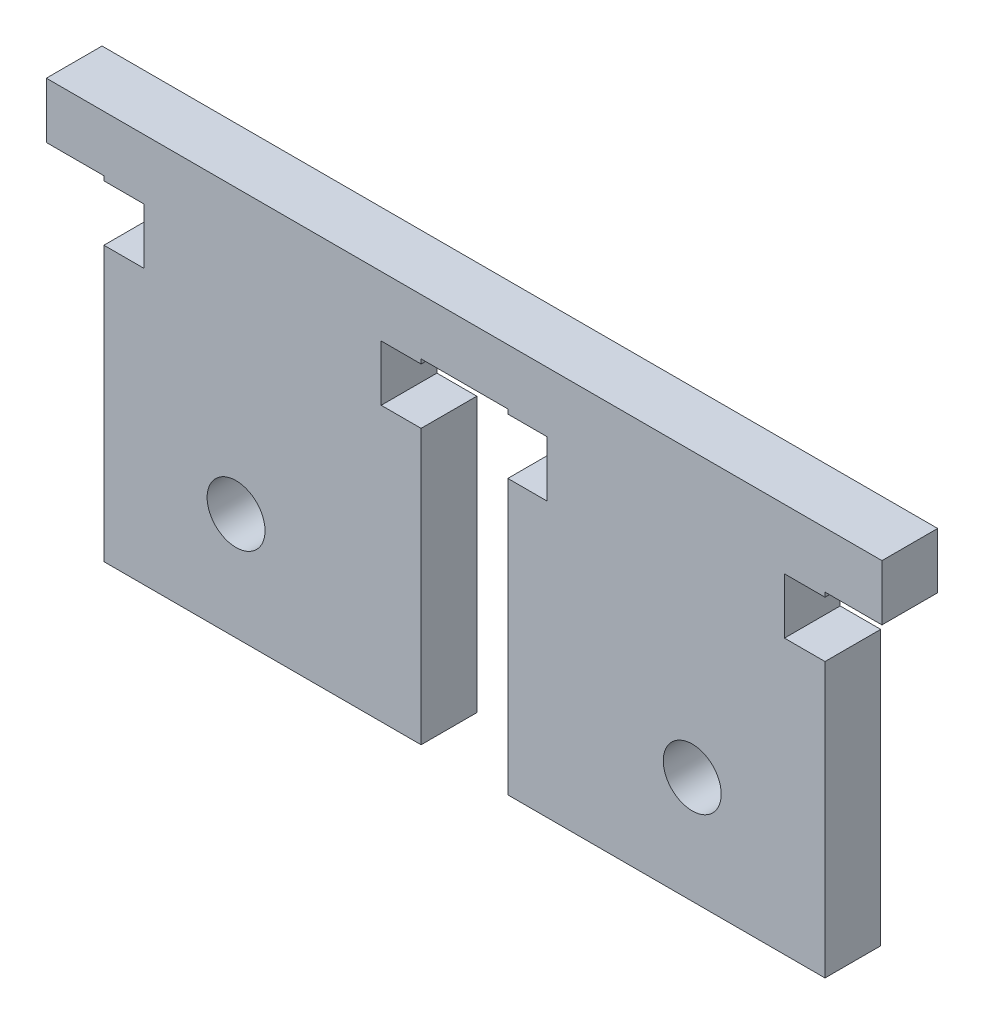
SolidWorks part; units mm, degrees
material "AISI 4130 Steel, annealed at 865C"
ref_plane "X-Y Datum" through (0, 0, 0) normal (0, 0, 1) x (1, 0, 0)
ref_plane "X-Z Datum" through (0, 0, 0) normal (0, 1, 0) x (1, 0, 0)
ref_plane "Y-Z Datum" through (0, 0, 0) normal (1, 0, 0) x (0, 0, -1)
sketch "Sketch3" plane through (0, 0, 0) normal (0, 0, 1) x (1, 0, 0)
  line L1 (-47.625, -30.48) -> (47.625, -30.48)
  line L2 (-47.625, -30.48) -> (-47.625, 30.48)
  line L3 (-47.625, 30.48) -> (47.625, 30.48)
  line L4 (47.625, -30.48) -> (47.625, 30.48)
  line L5 (-47.625, -30.48) -> (47.625, 30.48) construction
  line L6 (-47.625, 30.48) -> (47.625, -30.48) construction
  point P0 (0, 0)
  dimension "D1" = 95.25
  dimension "D2" = 60.96
extrude "Boss-Extrude1" add sketch "Sketch3" along normal blind 6.35
sketch "Sketch4" plane through (0, 0, 6.35) normal (0, 0, 1) x (1, 0, 0)
  line L0 (-47.625, 15.24) -> (-41.0616, 15.24)
  line L1 (-47.625, 30.48) -> (-47.625, -30.48) construction
  line L2 (-41.0616, 15.24) -> (-4.5491, 15.24)
  line L3 (-4.5491, 15.24) -> (4.6203, 15.24)
  line L4 (4.6203, 15.24) -> (41.1328, 15.24)
  line L5 (41.1328, 15.24) -> (47.625, 15.24)
  line L6 (47.625, -30.48) -> (47.625, 30.48) construction
  line L7 (0.0356, 15.24) -> (0.0356, -30.48) construction
  line L8 (-41.0616, 15.24) -> (-47.625, 15.24)
  line L9 (-41.0616, 15.24) -> (-41.0616, -30.48)
  line L10 (-41.0616, -30.48) -> (-47.625, -30.48)
  line L11 (-47.625, 15.24) -> (-47.625, -30.48)
  line L12 (-47.625, -30.48) -> (47.625, -30.48) construction
  line L13 (-1.5519, -16.0071) -> (1.6231, -16.0071)
  line L14 (-1.5519, -16.0071) -> (-1.5519, 0.7671)
  line L17 (-4.5491, 15.24) -> (4.6203, 15.24)
  line L19 (-4.9063, -30.48) -> (4.9774, -30.48)
  line L20 (-4.9063, -30.48) -> (-4.9063, 15.24)
  line L25 (-4.9063, 15.24) -> (4.9774, 15.24)
  line L26 (4.9774, -30.48) -> (4.9774, 15.24)
  line L27 (41.1328, 15.24) -> (47.625, 15.24)
  line L28 (41.1328, 15.24) -> (41.1328, -30.48)
  line L29 (41.1328, -30.48) -> (47.625, -30.48)
  line L31 (-4.9063, -30.48) -> (4.9774, 15.24) construction
  line L32 (-4.9063, 15.24) -> (4.9774, -30.48) construction
  line L33 (-1.5519, 0.7671) -> (1.6231, 0.7671)
  line L34 (1.6231, -16.0071) -> (1.6231, 0.7671)
  line L35 (-1.5519, -16.0071) -> (1.6231, 0.7671) construction
  line L36 (-1.5519, 0.7671) -> (1.6231, -16.0071) construction
  point P15 (0.0356, -7.62)
  point P20 (0.0356, -7.62)
  line M5 (47.625, -30.48) -> (47.625, 30.48)
  line M7 (-47.625, 30.48) -> (-47.625, -30.48)
  line M8 (-47.625, -30.48) -> (47.625, -30.48)
  dimension "D1" = 6.5634
  dimension "D2" = 36.5125
  dimension "D3" = 6.4922
  dimension "D4" = 36.5125
  dimension "D5" = 9.8837
  dimension "D6" = 45.72
  dimension "D7" = 3.175
  dimension "D9" = 45.72
extrude "Cut-Extrude1" cut sketch "Sketch4" against normal blind 6.35 contours L9 L0 M7 M8 | L5 L28 M8 M5 | L19 L26 L4 L3 L2 L20 L34 L13 L14 L33 | L13 L34 L33 L14 region at (-44.3433, -7.62, 6.35) region at (-4.7277, 14.7722, 6.35) region at (44.3789, -7.62, 6.35) region at (0.0356, -7.62, 6.35)
sketch "Sketch5" plane through (0, 0, 6.35) normal (0, 0, 1) x (1, 0, 0)
  line L9 (-22.984, -30.48) -> (-22.984, 30.48) construction
  line L10 (-41.275, 8.382) -> (-36.5125, 8.382)
  line L12 (-41.275, 14.732) -> (-36.5125, 14.732)
  line L13 (-36.5125, 8.382) -> (-36.5125, 14.732)
  line L14 (-41.0616, -30.48) -> (-4.9063, -30.48) construction
  line L15 (47.625, 30.48) -> (-47.625, 30.48) construction
  line L16 (-41.275, 14.732) -> (-47.6562, 14.732)
  line L17 (-4.6929, 8.382) -> (-9.4554, 8.382)
  line L18 (-4.6929, 8.382) -> (-4.6929, 14.732)
  line L19 (-4.6929, 14.732) -> (-9.4554, 14.732)
  line L20 (-9.4554, 8.382) -> (-9.4554, 14.732)
  line L22 (-41.275, 8.382) -> (-47.6562, 8.382)
  line L23 (-47.6562, 14.732) -> (-47.6562, 8.382)
  line M5 (-41.0616, 15.24) -> (-41.0616, -30.48)
  line M15 (-47.625, 30.48) -> (-47.625, 15.24)
  line M16 (-47.625, 15.24) -> (-41.0616, 15.24)
  dimension "D1" = 6.35
  dimension "D2" = 4.7625
  dimension "D3" = 15.748
extrude "Cut-Extrude2" cut sketch "Sketch5" against normal blind 6.35 contours L10 L13 L12 | L20 L17 L18 L19 | L16 L23 L22 M5 M16 M15 region at (-44.3589, 11.557, 6.35) region at (-38.7871, 11.557, 6.35) region at (-7.0742, 11.557, 6.35)
mirror "Mirror1" about plane through (0, 0, 0) normal (1, 0, 0) of "Cut-Extrude2"
sketch "Sketch8" [suppressed] plane through (0, 15.24, 0) normal (0, -1, 0) x (1, 0, 0)
  line L0 (-9.525, 3.175) -> (9.525, 3.175) construction
  line L1 (-9.525, 0) -> (-9.525, 6.35) construction
  line L2 (9.525, 0) -> (9.525, 6.35) construction
  line L3 (-4.7625, 6.35) -> (4.7625, 6.35) construction
  line L4 (-4.7625, 0) -> (4.7625, 0)
  line L5 (-4.7625, 0) -> (-4.7625, 6.35)
  line L6 (-4.7625, 6.35) -> (4.7625, 6.35)
  line L7 (4.7625, 0) -> (4.7625, 6.35)
  line L8 (-4.7625, 0) -> (4.7625, 6.35) construction
  line L9 (-4.7625, 6.35) -> (4.7625, 0) construction
  point P6 (0, 3.175)
  line M3 (-4.7625, 0) -> (4.7625, 0)
  dimension "D1" = 4.7625
extrude "Cut-Extrude3" [suppressed] cut sketch "Sketch8" against normal blind 1.5875 contours L7 L0 L5 M3
sketch "Sketch9" plane through (0, 30.48, 0) normal (0, 1, 0) x (1, 0, 0)
  line L1 (-47.625, 0) -> (47.625, 0)
  line L2 (-47.625, 0) -> (-47.625, -6.35)
  line L3 (-47.625, -6.35) -> (47.625, -6.35)
  line L4 (47.625, 0) -> (47.625, -6.35)
extrude "Cut-Extrude6" cut sketch "Sketch9" against normal blind 8.89
sketch "Sketch10" plane through (0, 0, 6.35) normal (0, 0, 1) x (1, 0, 0)
  line L0 (0, 0) -> (0, -30.2463) construction
  line L1 (-26, -10.6279) -> (26, -10.6279) construction
  circle A1 centre (-26, -10.6279) radius 3.3015
  circle A3 centre (26, -10.6279) radius 3.3015
  point P11 (0, -10.6279)
  dimension "D2" = 6.603
  dimension "D1" = 52
extrude "Cut-Extrude7" cut sketch "Sketch10" against normal blind 6.35
sketch "Sketch11" plane through (0, -30.48, 0) normal (0, -1, 0) x (1, 0, 0)
  line L1 (-41.0616, 6.35) -> (41.1328, 6.35)
  line L2 (-41.0616, 6.35) -> (-41.0616, 0)
  line L3 (-41.0616, 0) -> (41.1328, 0)
  line L4 (41.1328, 6.35) -> (41.1328, 0)
extrude "Cut-Extrude9" cut sketch "Sketch11" against normal blind 7.62
